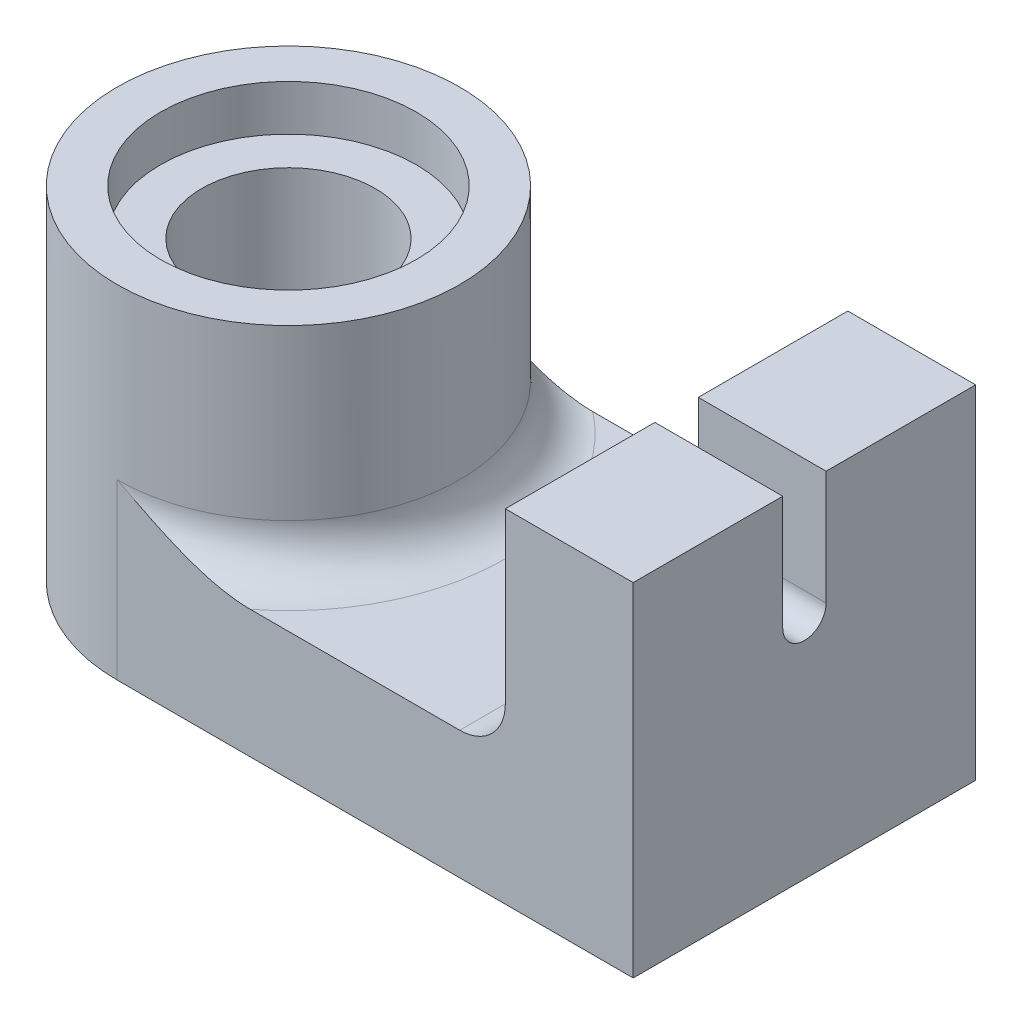
SolidWorks part; units mm, degrees
ref_plane "Front Plane" through (0, 0, 0) normal (0, 0, 1) x (1, 0, 0)
ref_plane "Top Plane" through (0, 0, 0) normal (0, 1, 0) x (1, 0, 0)
ref_plane "Right Plane" through (0, 0, 0) normal (1, 0, 0) x (0, 0, -1)
sketch "Sketch1" plane through (0, 0, 0) normal (0, 1, 0) x (1, 0, 0)
  line L1 (-56.5, -37.5) -> (56.5, -37.5)
  line L2 (-56.5, -37.5) -> (-56.5, 37.5)
  line L3 (-56.5, 37.5) -> (56.5, 37.5)
  line L4 (56.5, -37.5) -> (56.5, 37.5)
  line L5 (-56.5, -37.5) -> (56.5, 37.5) construction
  line L6 (-56.5, 37.5) -> (56.5, -37.5) construction
  circle A0 centre (-56.5, 0) radius 37.5
  point P0 (0, 0)
  dimension "D1" = 113
  dimension "D2" = 75
extrude "Boss-Extrude1" add sketch "Sketch1" along normal blind 75 contours L2 A0 | L2 A0 region at (-72.4155, 0, 0) region at (-40.5845, 0, 0)
extrude "Boss-Extrude2" add sketch "Sketch1<3>" along normal blind 28 contours L1 L4 L3 L2
sketch "Sketch1<3>" plane through (0, 0, 0) normal (0, 1, 0) x (1, 0, 0) same geometry as "Sketch1"
fillet "Fillet1" radius 10 1 edges at (-19, 28, 0)
sketch "Sketch2" plane through (0, 75, 0) normal (0, 1, 0) x (1, 0, 0)
  circle A0 centre (-56.5, 0) radius 28
  dimension "D1" = 56
extrude "Cut-Extrude1" cut sketch "Sketch2" against normal blind 10
sketch "Sketch3" plane through (0, 65, 0) normal (0, 1, 0) x (1, 0, 0)
  line L0 (-56.5, 0) -> (-56.5, 5)
  line L2 (-56.5, 5) -> (-34.5, 5)
  line L3 (-56.5, 5) -> (-56.5, -5)
  line L4 (-56.5, -5) -> (-34.5, -5)
  line L5 (-34.5, 5) -> (-34.5, -5)
  circle A0 centre (-56.5, 0) radius 19
  dimension "D1" = 38
  dimension "D2" = 5
  dimension "D3" = 10
  dimension "D4" = 22
extrude "Cut-Extrude2" cut sketch "Sketch3" against normal blind 119 contours L2 A0 L4 L3 L0 | L4 A0 L2 L0 L3 | A0 L4 L5 L2 region at (-58.3633, 65, 0) region at (-47.1098, 65, 0) region at (-36.117, 65, 0)
sketch "Sketch4" plane through (0, 0, 0) normal (0, -1, 0) x (1, 0, 0)
  circle A0 centre (-56.5, 0) radius 28
  dimension "D1" = 56
extrude "Cut-Extrude3" cut sketch "Sketch4" against normal blind 10
sketch "Sketch5" plane through (0, 28, 0) normal (0, 1, 0) x (1, 0, 0)
  line L0 (-56.5, -37.5) -> (56.5, -37.5) construction
  line L1 (56.5, 37.5) -> (28.5, 37.5)
  line L2 (56.5, 37.5) -> (56.5, -37.5)
  line L3 (56.5, -37.5) -> (28.5, -37.5)
  line L4 (28.5, 37.5) -> (28.5, -37.5)
  dimension "D1" = 28
extrude "Boss-Extrude3" add sketch "Sketch5" along normal blind 47
sketch "Sketch6" plane through (56.5, 0, 0) normal (1, 0, 0) x (0, 0, -1)
  line L0 (0, 75) -> (0, 50)
  line L1 (-37.5, 75) -> (37.5, 75) construction
  line L3 (-4.75, 50) -> (4.75, 50)
  line L4 (-4.75, 50) -> (-4.75, 75)
  line L5 (-4.75, 75) -> (4.75, 75)
  line L6 (4.75, 50) -> (4.75, 75)
  circle A0 centre (0, 50) radius 4.75
  line M9 (37.5, 75) -> (-37.5, 75)
  dimension "D2" = 9.5
  dimension "D1" = 25
extrude "Cut-Extrude4" cut sketch "Sketch6" against normal blind 47 contours A0 L0 L4 M9 | A0 L6 L0 M9 | L3 A0 L0 | L0 A0 L3 | L3 A0 region at (56.5, 64.3389, -2.438) region at (56.5, 64.3389, 2.438) region at (56.5, 52.016, -2.016) region at (56.5, 52.016, 2.016) region at (56.5, 47.984, 0)
fillet "Fillet2" radius 10 1 edges at (28.5, 28, 0)
